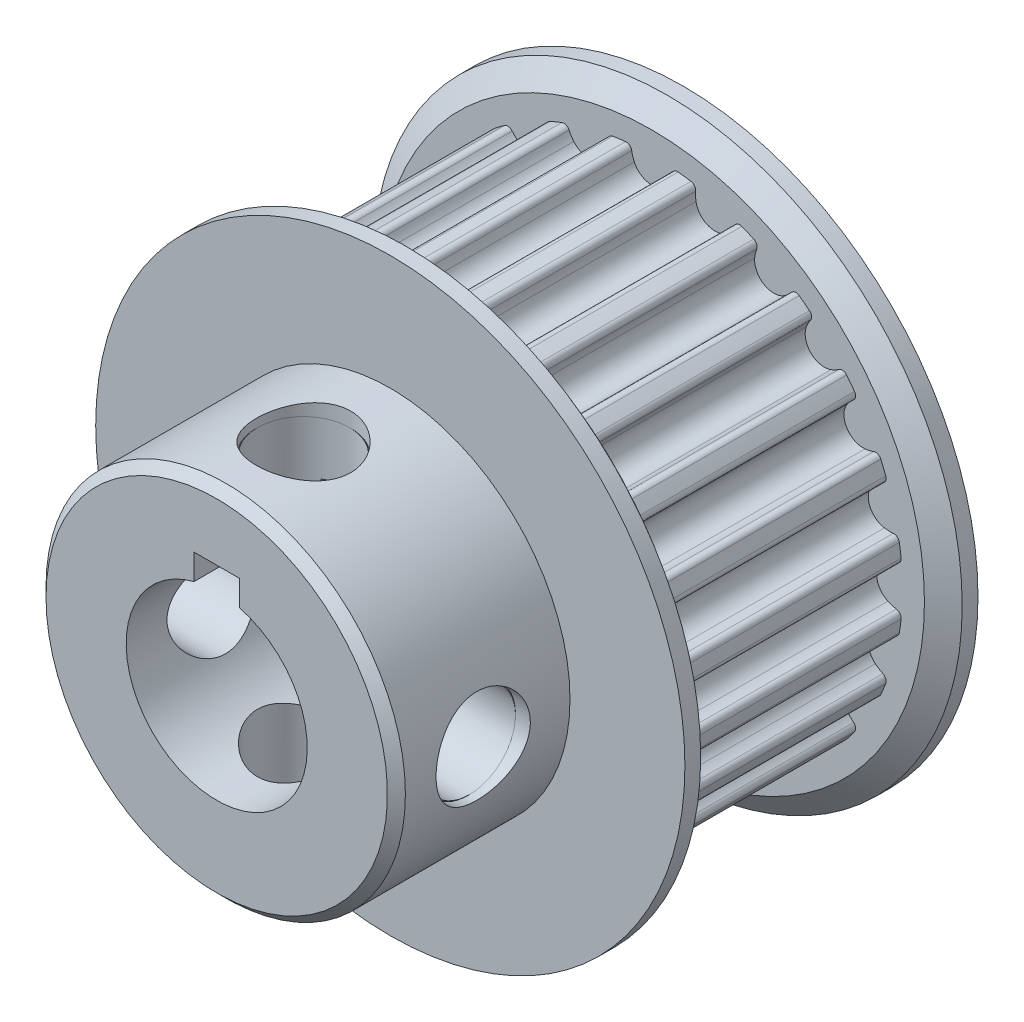
SolidWorks part; units mm, degrees
ref_plane "Front Plane" through (0, 0, 0) normal (0, 0, 1) x (1, 0, 0)
ref_plane "Top Plane" through (0, 0, 0) normal (0, 1, 0) x (1, 0, 0)
ref_plane "Right Plane" through (0, 0, 0) normal (1, 0, 0) x (0, 0, -1)
sketch "Sketch1" plane through (0, 0, 0) normal (0, 0, 1) x (1, 0, 0)
  line L1 (-2.6709, 9.9345) -> (2.6709, 9.9345) construction
  line L4 (0, 0) -> (0, 9.9345) construction
  line L5 (0, 9.9345) -> (0, 14.6064) construction
  line L6 (0, 11.4555) -> (2.9742, 11.0627) construction
  line L7 (2.9742, 11.0627) -> (4.1023, 10.7594) construction
  line L8 (2.9742, 11.0627) -> (2.6709, 9.9345) construction
  line L9 (-2.9742, 11.0627) -> (-2.6709, 9.9345) construction
  line L10 (-2.8753, 10.6947) -> (-3.4997, 13.0175)
  line L11 (-3.4997, 13.0175) -> (3.4997, 13.0175)
  line L12 (3.4997, 13.0175) -> (2.8753, 10.6947)
  circle A0 centre (0, 0) radius 11.4555 construction
  circle A1 centre (0, 0) radius 13.0175 construction
  circle A2 centre (0, 0) radius 11.0745 construction
  arc A3 (-0.7739, 10.4329) -> (0.7739, 10.4329) centre (0, 10.7845) ccw
  arc A4 (-0.7739, 10.4329) -> (-0.8885, 10.8068) centre (0.61, 11.0616) cw
  arc A5 (-2.8753, 10.6947) -> (-1.1612, 11.0135) centre (0, 0) cw
  arc A6 (-0.8885, 10.8068) -> (-1.1612, 11.0135) centre (-1.1349, 10.7648) ccw
  arc A7 (2.8753, 10.6947) -> (1.1612, 11.0135) centre (0, 0) ccw
  arc A8 (0.8885, 10.8068) -> (1.1612, 11.0135) centre (1.1349, 10.7648) cw
  arc A9 (0.7739, 10.4329) -> (0.8885, 10.8068) centre (-0.61, 11.0616) ccw
  point P6 (0, 20.9083)
  point P11 (0, 11.4555)
  point P13 (0, 13.0175)
  point P14 (0, 11.0745)
  dimension "D1" = 6.3019
  dimension "D2" = 3.1509
sketch "Sketch2" plane through (0, 0, 0) normal (1, 0, 0) x (0, 0, -1)
  line L0 (-10.31, 3.175) -> (10.31, 3.175)
  line L1 (-10.31, 3.175) -> (-10.31, 7.94)
  line L2 (-10.31, 7.94) -> (-2.64, 7.94)
  line L3 (-2.64, 7.94) -> (-2.64, 13.0175)
  line L4 (-2.64, 13.0175) -> (-1.245, 13.0175) construction
  line L5 (-1.245, 13.0175) -> (-1.245, 11.0745) construction
  line L6 (-1.245, 11.0745) -> (8.915, 11.0745)
  line L7 (8.915, 11.0745) -> (8.915, 13.0175) construction
  line L8 (8.915, 13.0175) -> (10.31, 13.0175) construction
  line L9 (10.31, 13.0175) -> (10.31, 3.175)
  line L10 (-10.31, 0) -> (10.31, 0) construction
  line L11 (9.6125, 13.0175) -> (8.915, 12.046)
  line L12 (-1.245, 12.046) -> (-1.9425, 13.0175)
  line L13 (-2.64, 13.0175) -> (-1.9425, 13.0175)
  line L14 (-1.245, 12.046) -> (-1.245, 11.0745)
  line L15 (8.915, 11.0745) -> (8.915, 12.046)
  line L16 (9.6125, 13.0175) -> (10.31, 13.0175)
  arc A0 (-1.245, 12.046) -> (-1.9425, 13.0175) centre (-2.2703, 12.046) ccw construction
  arc A1 (8.915, 12.046) -> (9.6125, 13.0175) centre (9.9403, 12.046) cw construction
  point P12 (-1.245, 12.046)
  point P14 (-1.9425, 13.0175)
  point P20 (8.915, 12.046)
  point P21 (9.6125, 13.0175)
  point P25 (8.915, 0)
  point P26 (-1.245, 0)
revolve "Revolve1" add sketch "Sketch2" angle 360 mid plane about L10
sketch "Sketch3" plane through (0, 0, 0) normal (0, 0, 1) x (1, 0, 0)
  line L6 (3.4997, 13.0175) -> (-3.4997, 13.0175)
  line L7 (2.8753, 10.6947) -> (3.4997, 13.0175)
  line L8 (-3.4997, 13.0175) -> (-2.8753, 10.6947)
  line L9 (3.4997, 13.0175) -> (-3.4997, 13.0175)
  line L10 (2.8753, 10.6947) -> (3.4997, 13.0175)
  line L11 (-3.4997, 13.0175) -> (-2.8753, 10.6947)
  arc A8 (2.8753, 10.6947) -> (1.1612, 11.0135) centre (0, 0) ccw
  arc A9 (1.1612, 11.0135) -> (0.8885, 10.8068) centre (1.1349, 10.7648) ccw
  arc A10 (0.7739, 10.4329) -> (0.8885, 10.8068) centre (-0.61, 11.0616) ccw
  arc A11 (-0.7739, 10.4329) -> (0.7739, 10.4329) centre (0, 10.7845) ccw
  arc A12 (-0.8885, 10.8068) -> (-0.7739, 10.4329) centre (0.61, 11.0616) ccw
  arc A13 (-0.8885, 10.8068) -> (-1.1612, 11.0135) centre (-1.1349, 10.7648) ccw
  arc A14 (-1.1612, 11.0135) -> (-2.8753, 10.6947) centre (0, 0) ccw
  arc A15 (2.8753, 10.6947) -> (1.1612, 11.0135) centre (0, 0) ccw
  arc A16 (1.1612, 11.0135) -> (0.8885, 10.8068) centre (1.1349, 10.7648) ccw
  arc A17 (0.7739, 10.4329) -> (0.8885, 10.8068) centre (-0.61, 11.0616) ccw
  arc A18 (-0.7739, 10.4329) -> (0.7739, 10.4329) centre (0, 10.7845) ccw
  arc A19 (-0.8885, 10.8068) -> (-0.7739, 10.4329) centre (0.61, 11.0616) ccw
  arc A20 (-0.8885, 10.8068) -> (-1.1612, 11.0135) centre (-1.1349, 10.7648) ccw
  arc A21 (-1.1612, 11.0135) -> (-2.8753, 10.6947) centre (0, 0) ccw
  dimension "D1" = 0
extrude "Cut-Extrude1" cut sketch "Sketch3" against normal up to vertex (8.915 mm away) from vertex up to point (0, 11.0745, -8.915) starting at point (0, 11.0745, 1.245)
pattern_circular "CirPattern1" count 24 over 360 about axis through (0, 0, 10.31) along (0, 0, 1) of "Cut-Extrude1"
sketch "Sketch4" plane through (0, 0, 0) normal (1, 0, 0) x (0, -1, 0)
  line L0 (0, -2.64) -> (0, -10.31) construction
  line L1 (-7.94, -2.64) -> (7.94, -2.64) construction
  line L2 (-7.94, -10.31) -> (7.94, -10.31) construction
  circle A0 centre (0, -6.475) radius 2.0828
extrude "Cut-Extrude2" cut sketch "Sketch4" along normal through all
ref_plane "Plane1" through (0, 0, 6.475) normal (0, 0, 1) x (1, 0, 0)
sketch "Sketch5" plane through (0, 0, 6.475) normal (0, 0, 1) x (1, 0, 0)
  line L0 (0, 0.1664) -> (0, 7.94) construction
  line L1 (3.175, -1.7018) -> (3.175, 0)
  line L2 (3.556, -2.0828) -> (7.281, -2.0828)
  line L3 (3.175, 0) -> (7.94, 0) construction
  line L4 (3.175, 0) -> (7.662, 0)
  line L5 (7.662, 0) -> (7.662, -1.7018)
  line L6 (3.556, -2.0828) -> (3.175, -1.7018)
  line L7 (7.662, -1.7018) -> (7.281, -2.0828)
  circle A0 centre (0, 0) radius 7.94 construction
  circle A1 centre (0, 0) radius 3.175 construction
  point P2 (3.175, -2.0828)
  point P11 (7.662, -2.0828)
revolve "Revolve2" add sketch "Sketch5" angle 360 mid plane about L4
sketch "Sketch6" plane through (7.662, 5.3841, 0) normal (-1, 0, 0) x (0, -1, 0)
  line L1 (5.3841, 7.6775) -> (4.3427, 7.0763)
  line L2 (4.3427, 7.0763) -> (4.3427, 5.8737)
  line L3 (4.3427, 5.8737) -> (5.3841, 5.2725)
  line L4 (5.3841, 5.2725) -> (6.4255, 5.8737)
  line L5 (6.4255, 5.8737) -> (6.4255, 7.0763)
  line L6 (6.4255, 7.0763) -> (5.3841, 7.6775)
  circle A0 centre (5.3841, 6.475) radius 1.0414 construction
  dimension "D1" = 2.0828
extrude "Cut-Extrude3" cut sketch "Sketch6" along normal blind 1.5621
pattern_circular "CirPattern2" count 2 over 90 about axis through (0, 0, 10.31) along (0, 0, 1) of "Cut-Extrude2", "Revolve2", "Cut-Extrude3"
chamfer "Chamfer1" distance 0.397 angle 45 2 edges at (3.175, 0, 10.31) (7.94, 0, 10.31)
ref_axis "Center Axis 1" through (0, 0, -10.31) along (0, 0, 1)
ref_plane "Contact Plane 1" through (0, 0, 10.31) normal (0, 0, 1) x (1, 0, 0)
ref_plane "Contact Plane 2" through (0, 0, -10.31) normal (0, 0, -1) x (-1, 0, 0)
sketch "Sketch7" plane through (0, 0, 10.31) normal (0, 0, 1) x (1, 0, 0)
  circle A0 centre (0, 0) radius 4.7625
  dimension "D1" = 9.525
sketch "Sketch8" plane through (0, 0, -10.31) normal (0, 0, -1) x (-1, 0, 0)
  circle A0 centre (0, 0) radius 7.94
  dimension "D1" = 15.8801
extrude "Boss-Extrude1" [suppressed] add sketch "Sketch8" along normal blind 7.6708 contours A0
sketch "Sketch9" plane through (0, 0, 10.31) normal (0, 0, 1) x (1, 0, 0)
  circle A0 centre (0, 0) radius 4
  dimension "D1" = 8
extrude "Cut-Extrude6" cut sketch "Sketch9" against normal through all both and the other way through all
sketch "Sketch10" plane through (7.662, 0, 0) normal (1, 0, 0) x (0, 0, -1)
  circle A0 centre (-6.475, 0) radius 2.032
  dimension "D1" = 4.064
extrude "Cut-Extrude7" cut sketch "Sketch10" against normal through all both and the other way through all
sketch "Sketch11" plane through (0, 7.662, 0) normal (0, 1, 0) x (1, 0, 0)
  circle A0 centre (0, -6.475) radius 2.032
  dimension "D1" = 4.064
extrude "Cut-Extrude8" cut sketch "Sketch11" against normal blind 20.828
sketch "Sketch12" plane through (0, 0, 10.31) normal (0, 0, 1) x (1, 0, 0)
  line L1 (-1, 3) -> (1, 3)
  line L2 (-1, 3) -> (-1, 5)
  line L3 (-1, 5) -> (1, 5)
  line L4 (1, 3) -> (1, 5)
  line L5 (-1, 3) -> (1, 5) construction
  line L6 (-1, 5) -> (1, 3) construction
  circle A0 centre (0, 0) radius 4 construction
  point P0 (0, 4)
  dimension "D1" = 2
  dimension "D2" = 2
extrude "Cut-Extrude9" cut sketch "Sketch12" against normal through all both and the other way through all
equation "\"D2@Sketch1\" = \"D1@Sketch1\"/2"
equation "\"D1@Sketch6\" = \"Set Screw@Sketch4\" / 2"
equation "\"D1@Cut-Extrude3\" = \"D1@Sketch6\"*.75"
equation "\"D1@Chamfer1\"=\"Hub Dia@Sketch2\"*.025"
